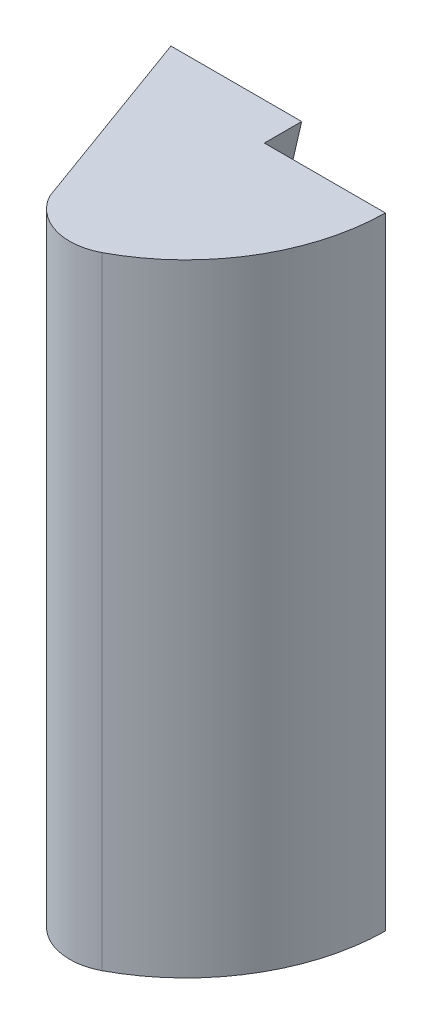
SolidWorks part; units mm, degrees
ref_plane "Front Plane" through (0, 0, 0) normal (0, 0, 1) x (1, 0, 0)
ref_plane "Top Plane" through (0, 0, 0) normal (0, 1, 0) x (1, 0, 0)
ref_plane "Right Plane" through (0, 0, 0) normal (1, 0, 0) x (0, 0, -1)
sketch "Sketch1" plane through (0, 0, 0) normal (0, 1, 0) x (1, 0, 0)
  line L0 (13.1596, 18.7939) -> (-6.8404, 18.7939)
  line L1 (-6.8404, 18.7939) -> (0, 0)
  arc A1 (0, 0) -> (13.1596, 18.7939) centre (-2.8171, 15.9767) ccw
  dimension "D1" = 70
  dimension "D2" = 20
  dimension "D3" = 20
extrude "Boss-Extrude1" add sketch "Sketch1" along normal blind 50
sketch "Sketch3" plane through (0, 0, -18.7939) normal (0, 0, -1) x (-1, 0, 0)
  line L0 (-13.1596, 0) -> (6.8404, 0) construction
  line L1 (-13.1596, 50) -> (6.8404, 50) construction
  line L2 (6.8404, 50) -> (6.8404, 0) construction
  circle A0 centre (-3.1596, 20) radius 1.6
  circle A1 centre (-3.1596, 30) radius 1.6
  dimension "D1" = 3.2
  dimension "D2" = 3.2
  dimension "D3" = 10
  dimension "D4" = 20
  dimension "D5" = 20
  dimension "D6" = 10
sketch "Sketch5" plane through (0, 50, 0) normal (0, 1, 0) x (1, 0, 0)
  line L0 (-6.8404, 18.7939) -> (0, 0) construction
  line L1 (-1.2659, 3.4781) -> (-6.8404, 18.7939)
  line L2 (-6.8404, 18.7939) -> (13.1596, 18.7939)
  arc A0 (-1.2659, 3.4781) -> (4.8351, 1.6716) centre (2.6878, 5.6254) ccw
  arc A1 (0, 0) -> (13.1596, 18.7939) centre (-2.8171, 15.9767) ccw construction
  arc A2 (13.1596, 18.7939) -> (0, 0) centre (-2.8171, 15.9767) cw
  arc M1 (0, 0) -> (13.1596, 18.7939) centre (-2.8171, 15.9767) ccw
  line M3 (-6.8404, 18.7939) -> (0, 0)
extrude "Cut-Extrude1" cut sketch "Sketch5" against normal blind 50 contours A0 M3 M1 region at (0.8039, 50, -1.1091)
extrude "Cut-Extrude2" cut sketch "Sketch3" against normal blind 15 contours A0 | A1
sketch "Sketch6" plane through (0, 0, -18.7939) normal (0, 0, -1) x (-1, 0, 0)
  line L0 (-3.1596, 30) -> (-7.777, 50) construction
  line L1 (-13.1596, 50) -> (6.8404, 50) construction
  line L2 (-13.1596, 50) -> (-13.1596, 0) construction
  line L3 (-5.4683, 40) -> (-1.5708, 40.8998) construction
  line L4 (-3.1596, 30) -> (0.7379, 30.8998) construction
  line L5 (0.7379, 30.8998) -> (-1.5708, 40.8998)
  line L6 (-1.5708, 40.8998) -> (-3.6717, 50)
  line L7 (-3.6717, 50) -> (-7.777, 50)
  line L8 (-7.777, 50) -> (-13.1596, 50)
  line L9 (0.9456, 30) -> (-3.1596, 30) construction
  line L10 (0.9456, 30) -> (0.7379, 30.8998) construction
  line L11 (0.7379, 30.8998) -> (0.9456, 30)
  line L12 (-3.1596, 30) -> (-3.1596, 20) construction
  line L13 (-3.1596, 25) -> (6.8404, 25) construction
  line L14 (6.8404, 50) -> (6.8404, 0) construction
  line L15 (6.8404, 25) -> (-13.1596, 25) construction
  line L16 (0.9456, 30) -> (0.9456, 20)
  line L17 (0.9456, 30) -> (0.9456, 35)
  line L18 (0.9456, 35) -> (-0.2087, 35)
  line L19 (0.7379, 19.1002) -> (0.9456, 20)
  line L20 (0.9456, 20) -> (0.9456, 15)
  line L21 (0.9456, 15) -> (-0.2087, 15)
  line L22 (0.7379, 19.1002) -> (-1.5708, 9.1002)
  line L23 (-1.5708, 9.1002) -> (-3.6717, 0)
  line L24 (-3.6717, 0) -> (-7.777, 0)
  line L25 (-7.777, 0) -> (-13.1596, 0)
  line L26 (-13.1596, 0) -> (-13.1596, 50)
  line L28 (0.9456, 35) -> (1.9456, 35)
  line L29 (0.9456, 35) -> (0.9456, 15)
  line L30 (0.9456, 15) -> (1.9456, 15)
  line L31 (1.9456, 35) -> (1.9456, 15)
  point P26 (0.9456, 25)
  circle M14 centre (-3.1596, 20) radius 1.6
  circle M15 centre (-3.1596, 30) radius 1.6
  line M16 (-13.1596, 0) -> (6.8404, 0)
  line M18 (6.8404, 50) -> (-13.1596, 50)
  line M19 (-13.1596, 50) -> (-13.1596, 0)
  dimension "D1" = 13
  dimension "D2" = 4
  dimension "D3" = 4
  dimension "D4" = 90
  dimension "D5" = 5
  dimension "D6" = 1
extrude "Cut-Extrude4" cut sketch "Sketch6" against normal blind 3 contours L23 L22 L19 L16 L11 L5 L6 M18 M19 M16 M15 M14 | L17 L18 L5 L11 | L19 L22 L21 L20 region at (7.0395, 25, -18.7939) region at (-0.5608, 33.3333, -18.7939) region at (-0.5608, 16.6667, -18.7939)
sketch "Sketch7" plane through (0, 0, -18.7939) normal (0, 0, -1) x (-1, 0, 0)
  line L1 (-13.1596, 0) -> (-14.8261, 0)
  line L2 (-13.1596, 0) -> (-13.1596, 50)
  line L3 (-13.1596, 50) -> (-14.8261, 50)
  line L4 (-14.8261, 0) -> (-14.8261, 50)
extrude "Cut-Extrude5" cut sketch "Sketch7" against normal blind 3
extrude "Cut-Extrude6" cut sketch "Sketch6<5>" against normal blind 3 contours L31 L28 L17 L16 L20 L30 region at (-1.4456, 25, -18.7939)
sketch "Sketch6<5>" plane through (0, 0, -18.7939) normal (0, 0, -1) x (-1, 0, 0) same geometry as "Sketch6"
